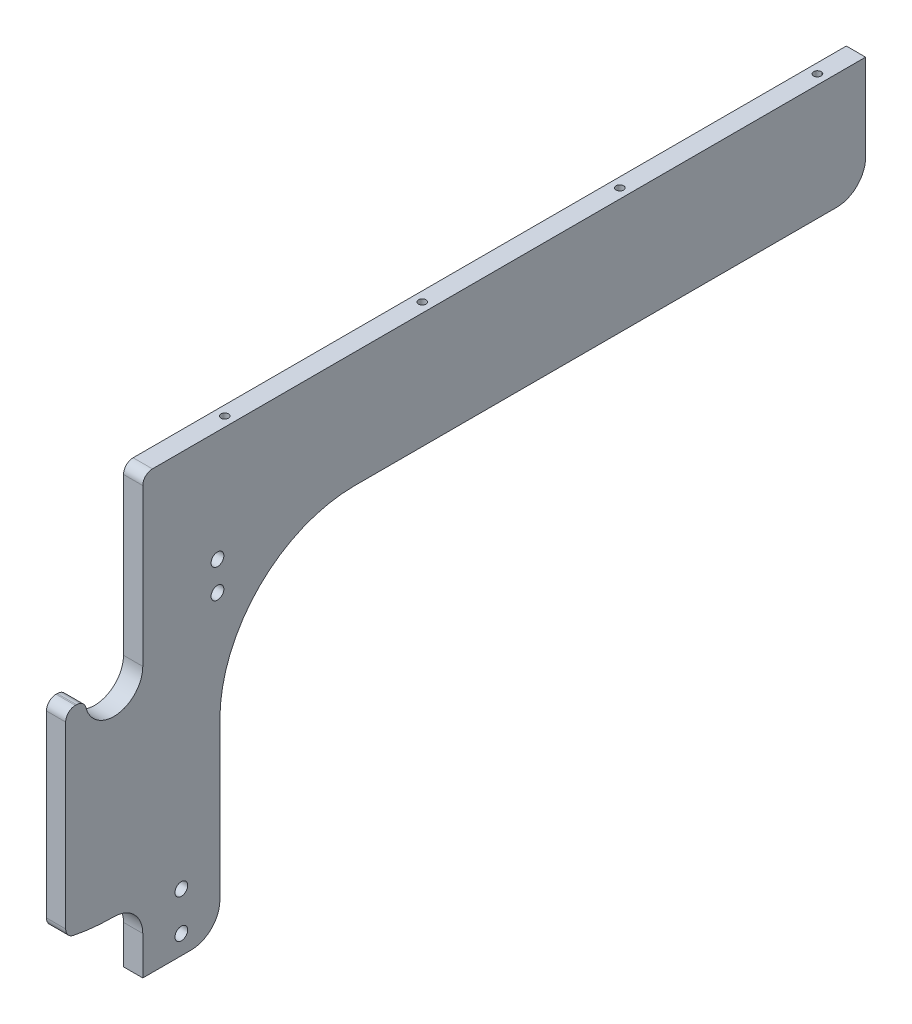
SolidWorks part; units mm, degrees
material "Alum 6061 (Default)"
ref_plane "Front Plane" through (0, 0, 0) normal (0, 0, 1) x (1, 0, 0)
ref_plane "Top Plane" through (0, 0, 0) normal (0, 1, 0) x (1, 0, 0)
ref_plane "Right Plane" through (0, 0, 0) normal (1, 0, 0) x (0, 0, -1)
sketch "Sketch1" plane through (0, 0, 0) normal (0, 0, 1) x (1, 0, 0)
  line L1 (-6.35, 143.6687) -> (6.35, 143.6687)
  line L2 (-6.35, 143.6687) -> (-6.35, -143.6687)
  line L3 (-6.35, -143.6687) -> (6.35, -143.6687)
  line L4 (6.35, 143.6687) -> (6.35, -143.6687)
  line L5 (-6.35, 143.6687) -> (6.35, -143.6687) construction
  line L6 (-6.35, -143.6687) -> (6.35, 143.6687) construction
  point P0 (0, 0)
  dimension "Width" = 12.7
  dimension "Height" = 287.3375
extrude "Extrude1" add sketch "Sketch1" along normal mid plane 527.05
sketch "Sketch3" plane through (6.35, 0, 0) normal (1, 0, 0) x (0, 0, -1)
  line L0 (-263.525, 143.6687) -> (263.525, 143.6687) construction
  line L1 (-263.525, -143.6687) -> (-263.525, 143.6687) construction
  line L2 (-263.525, 143.6687) -> (263.525, 143.6687) construction
  line L3 (-250.825, 34.1312) -> (-250.825, 143.6687)
  line L4 (-250.825, 143.6687) -> (-212.725, 143.6687)
  line L7 (-212.725, 143.6687) -> (-212.725, 34.1312)
  arc A0 (-250.825, 34.1312) -> (-212.725, 34.1312) centre (-231.775, 34.1312) ccw
  dimension "D5" = 38.1
  dimension "D1" = 109.5375
  dimension "D2" = 31.75
extrude "Extrude3" cut sketch "Sketch3" against normal up to next
sketch "Sketch10" plane through (6.35, 0, 0) normal (1, 0, 0) x (0, 0, -1)
  line L0 (-250.825, 143.6687) -> (-250.825, 34.1312) construction
  line L1 (-263.525, 143.6687) -> (-250.825, 143.6687)
  line L2 (-263.525, 143.6687) -> (-263.525, 34.1312)
  line L3 (-263.525, 34.1312) -> (-250.825, 34.1312)
  line L4 (-250.825, 143.6687) -> (-250.825, 34.1312)
  arc A0 (-250.825, 34.1312) -> (-212.725, 34.1312) centre (-231.775, 34.1312) ccw construction
  dimension "D1" = 0
extrude "Cut-Extrude4" cut sketch "Sketch10" against normal up to next
hole_wizard "M6x1.0 Tapped Hole1" positions "Sketch5" profile "Sketch4" tap size "M6x1.0" standard "ANSI Metric"
sketch "Sketch5" plane through (0, 143.6687, 0) normal (0, 1, 0) x (-1, 0, 0)
  line L0 (-6.35, -263.525) -> (6.35, -263.525) construction
  line L2 (0, -238.125) -> (0, -107.95) construction
  line L3 (0, -107.95) -> (0, 22.225) construction
  line L4 (0, 22.225) -> (0, 152.4) construction
  line L5 (6.35, 212.725) -> (-6.35, 212.725) construction
  point P0 (0, -238.125)
  point P1 (0, -107.95)
  point P3 (0, 22.225)
  point P5 (0, 152.4)
  point P23 (0, 212.725)
  dimension "D1" = 25.4
  dimension "D2" = 60.325
sketch "Sketch4" plane through (0, 143.6687, -238.125) normal (1, 0, 0) x (0, 0, 1)
  line L0 (0, 0) -> (0, 16.4882)
  line L1 (0, 16.4882) -> (2.5, 14.986)
  line L2 (2.5, 14.986) -> (2.5, 0)
  line L5 (2.5, 0) -> (0, 0)
  line L10 (0, 16.4882) -> (-2.5, 14.986) construction
  line L11 (0, -6.35) -> (0, 107.95) construction
  dimension "Tap Drill Dia." = 5
  dimension "Tap Drill Depth" = 14.986
  dimension "Drill Angle" = 118
cosmetic thread "Hole Thread2" parameters "D1"=11.938, "D2"=6
cosmetic thread "Hole Thread3" parameters "D1"=11.938, "D2"=6
cosmetic thread "Hole Thread4" parameters "D1"=11.938, "D2"=6
cosmetic thread "Hole Thread5" parameters "D1"=11.938, "D2"=6
sketch "Sketch7" plane through (6.35, 0, 0) normal (1, 0, 0) x (0, 0, -1)
  line L0 (-231.775, 34.1312) -> (-231.775, -118.2688) construction
  line L1 (-263.525, 34.1312) -> (-263.525, -143.6687) construction
  line L2 (-212.725, -118.2688) -> (-212.725, -143.6687)
  line L3 (-263.525, -143.6687) -> (263.525, -143.6687) construction
  line L4 (-212.725, -143.6687) -> (-263.525, -143.6687)
  line L9 (-263.525, -95.3838) -> (-263.525, -143.6687)
  arc A4 (-212.725, -118.2688) -> (-231.775, -99.2188) centre (-231.775, -118.2688) ccw
  arc A5 (-250.825, 34.1312) -> (-212.725, 34.1312) centre (-231.775, 34.1312) ccw construction
  arc A7 (-263.525, -95.3838) -> (-231.775, -99.2188) centre (-231.775, 34.1312) ccw
  dimension "D2" = 133.35
  dimension "D1" = 152.4
extrude "Cut-Extrude1" cut sketch "Sketch7" against normal up to next
fillet "Fillet2" radius 6.35 4 edges at (0, 143.6687, 212.725) (0, 34.1312, 263.525) (0, 34.1312, 250.825) (0, -95.3838, 263.525)
sketch "Sketch8" plane through (6.35, 0, 0) normal (1, 0, 0) x (0, 0, -1)
  line L1 (-212.725, -143.6687) -> (263.525, -143.6687) construction
  line L2 (263.525, -143.6687) -> (263.525, 143.6687) construction
  line L3 (263.525, 67.4688) -> (263.525, -143.6687)
  line L4 (263.525, -143.6687) -> (-161.925, -143.6687)
  line L5 (-206.375, 143.6687) -> (263.525, 143.6687) construction
  line L6 (263.525, 67.4688) -> (-73.025, 67.4687)
  line L8 (-263.525, -90.3028) -> (-263.525, 27.7812) construction
  line L9 (-161.925, -143.6687) -> (-161.925, -21.4313)
  arc A1 (-161.925, -21.4313) -> (-73.025, 67.4687) centre (-73.025, -21.4313) cw
  dimension "D4" = 88.9
  dimension "D1" = 76.2
  dimension "D3" = 101.6
extrude "Cut-Extrude2" cut sketch "Sketch8" against normal up to next
sketch "Sketch11" plane through (-6.35, 0, 0) normal (1, 0, 0) x (0, 0, -1)
  line L1 (-73.025, 80.1687) -> (244.475, 80.1687)
  line L2 (244.475, 124.6188) -> (-145.7261, 124.6187)
  line L3 (-206.375, 143.6687) -> (263.525, 143.6687) construction
  line L4 (-263.525, 27.7812) -> (-263.525, -90.3028) construction
  line L6 (-200.025, 55.1297) -> (-200.025, 34.1312)
  line L9 (-180.975, -80.1688) -> (-244.475, -80.1688)
  line L10 (-250.825, -3.9688) -> (-250.825, -73.8188)
  line L11 (250.825, 118.2688) -> (250.825, 86.5187)
  line L12 (263.525, 143.6687) -> (263.525, 67.4688) construction
  line L13 (-210.8651, 141.8089) -> (-135.8868, 41.4305) construction
  line L14 (-73.025, 67.4687) -> (263.525, 67.4687) construction
  line L15 (-174.625, -21.4313) -> (-174.625, -73.8188)
  line L16 (-150.8135, 114.4687) -> (-120.592, 74.0092)
  line L17 (-188.5876, 58.9298) -> (-165.6594, 28.2344)
  line L18 (-231.775, 2.3813) -> (-244.475, 2.3812)
  line L19 (-212.725, 137.3187) -> (-212.725, 34.1312) construction
  arc A1 (244.475, 80.1687) -> (250.825, 86.5187) centre (244.475, 86.5187) ccw
  arc A5 (-200.025, 55.1297) -> (-188.5876, 58.9298) centre (-193.675, 55.1297) cw
  arc A6 (-231.775, 2.3813) -> (-200.025, 34.1312) centre (-231.775, 34.1312) ccw
  arc A7 (-212.725, -118.2688) -> (-231.775, -99.2188) centre (-231.775, -118.2688) ccw construction
  arc A12 (244.475, 124.6188) -> (250.825, 118.2688) centre (244.475, 118.2688) cw
  arc A14 (-244.475, -80.1688) -> (-250.825, -73.8188) centre (-244.475, -73.8188) cw
  arc A15 (-180.975, -80.1688) -> (-174.625, -73.8188) centre (-180.975, -73.8188) ccw
  arc A16 (-73.025, 80.1687) -> (-174.625, -21.4313) centre (-73.025, -21.4313) ccw
  arc A17 (-73.025, 80.1687) -> (-113.0058, 71.9716) centre (-73.025, -21.4313) ccw
  arc A18 (-73.025, 67.4687) -> (-161.925, -21.4313) centre (-73.025, -21.4313) ccw construction
  arc A19 (-164.9985, 21.7363) -> (-174.625, -21.4313) centre (-73.025, -21.4313) ccw
  arc A21 (-145.7261, 124.6187) -> (-150.8135, 114.4687) centre (-145.7261, 118.2687) ccw
  arc A22 (-113.0058, 71.9716) -> (-120.592, 74.0092) centre (-115.5046, 77.8093) cw
  arc A23 (-164.9985, 21.7363) -> (-165.6594, 28.2344) centre (-170.7468, 24.4343) ccw
  arc A24 (-250.2201, 29.3687) -> (-212.725, 34.1312) centre (-231.775, 34.1312) ccw construction
  arc A25 (-250.825, -3.9688) -> (-244.475, 2.3812) centre (-244.475, -3.9688) cw
  arc A26 (-206.375, 143.6687) -> (-212.725, 137.3187) centre (-206.375, 137.3187) ccw construction
  dimension "D4" = 12.7
  dimension "D5" = 6.35
  dimension "D7" = 12.7
  dimension "D8" = 38.1
  dimension "D9" = 6.35
  dimension "D10" = 12.7
  dimension "D2" = 6.35
  dimension "D12" = 6.35
  dimension "D13" = 6.35
  dimension "D15" = 6.35
  dimension "D1" = 19.05
  dimension "D3" = 31.75
  dimension "D6" = 12.7
  dimension "D11" = 12.7
extrude "Cut-Extrude5" cut sketch "Sketch11" along normal blind 9.525
fillet "Fillet3" radius 4.7625 44 edges at (3.175, 124.6187, -49.3744) (3.175, 102.3937, -250.825) (3.175, 80.1687, -85.725) (-6.35, 124.6187, -49.3744) (-6.35, 102.3937, -250.825) (-6.35, 80.1687, -85.725) (-6.35, -80.1688, 212.725) (-6.35, -38.8938, 250.825) (-6.35, 11.6806, 209.3244) (3.175, -38.8938, 250.825) (3.175, -80.1688, 212.725) (3.175, 11.6806, 209.3244) (-6.35, 78.0984, 93.4312) (-6.35, -47.625, 174.625) (-6.35, -78.3089, 176.4849) (-6.35, 122.7589, -248.9651) (-6.35, 82.0286, -248.9651) (3.175, -78.3089, 176.4849) (3.175, -47.625, 174.625) (3.175, 78.0984, 93.4312) (3.175, 82.0286, -248.9651) (3.175, 122.7589, -248.9651) (-6.35, -78.3089, 248.9651) (3.175, -78.3089, 248.9651) (3.175, 94.2389, 135.7028) (-6.35, 71.6766, 117.1518) (-6.35, 94.2389, 135.7028) (-6.35, 121.1141, 151.403) (3.175, 121.1141, 151.403) (3.175, 71.6766, 117.1518) (-6.35, 0.5214, 248.9651) (-6.35, 2.3812, 238.125) (-6.35, 43.5821, 177.1235) (-6.35, 25.0768, 164.4294) (3.175, 2.3813, 238.125) (3.175, 0.5214, 248.9651) (3.175, 0.6827, 172.1892) (3.175, 25.0768, 164.4294) (3.175, 43.5821, 177.1235) (-6.35, 0.6827, 172.1892) (-6.35, 44.6305, 200.025) (-6.35, 61.1558, 195.6772) (3.175, 61.1558, 195.6772) (3.175, 44.6305, 200.025)
fillet "Fillet4" radius 19.05 2 edges at (0, 67.4688, -263.525) (0, -143.6687, 161.925)
hole_wizard "M8 Clearance Hole1" positions "Sketch12" profile "Sketch13" hole size "M8" standard "ANSI Metric" end condition up to next
sketch "Sketch12" plane through (-6.35, 0, 0) normal (-1, 0, 0) x (0, 0, 1)
  line L0 (263.525, 27.7812) -> (263.525, -90.3028) construction
  line L1 (206.375, 143.6687) -> (-263.525, 143.6687) construction
  line L2 (212.725, -143.6687) -> (180.975, -143.6687) construction
  point P0 (163.5125, 70.6437)
  point P2 (163.5125, 51.5937)
  point P4 (187.325, -105.5688)
  point P6 (187.325, -130.9688)
  dimension "D1" = 19.05
  dimension "D2" = 100.0125
  dimension "D3" = 73.025
  dimension "D4" = 12.7
  dimension "D5" = 76.2
  dimension "D6" = 25.4
sketch "Sketch13" plane through (-6.35, 70.6437, 163.5125) normal (0, 1, 0) x (0, 0, 1)
  line L0 (0, 0) -> (0, 12.7)
  line L1 (0, 12.7) -> (4.2, 12.7)
  line L2 (4.2, 12.7) -> (4.2, 0)
  line L5 (4.2, 0) -> (0, 0)
  line L11 (0, -6.35) -> (0, 107.95) construction
  dimension "Thru Hole Dia." = 8.4
  dimension "Thru Hole Depth" = 12.7
